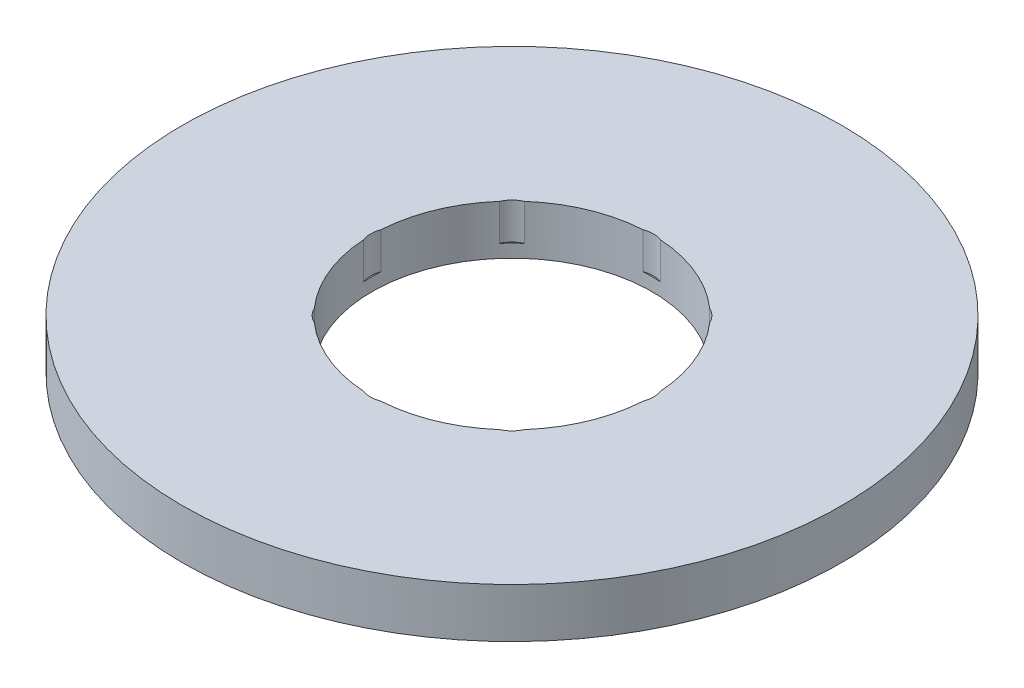
SolidWorks part; units mm, degrees
ref_plane "Front Plane" through (0, 0, 0) normal (0, 0, 1) x (1, 0, 0)
ref_plane "Top Plane" through (0, 0, 0) normal (0, 1, 0) x (1, 0, 0)
ref_plane "Right Plane" through (0, 0, 0) normal (1, 0, 0) x (0, 0, -1)
sketch "Sketch1" plane through (0, 0, 0) normal (0, 1, 0) x (1, 0, 0)
  circle A0 centre (0, 0) radius 100
  dimension "FLANGE_OD" = 200
extrude "Boss-Extrude1" add sketch "Sketch1" along normal blind 15
sketch "Sketch2" plane through (0, 0, 0) normal (0, 1, 0) x (1, 0, 0)
  circle A0 centre (0, 0) radius 42.5
  dimension "BORE_D" = 85
extrude "Cut-Extrude1" cut sketch "Sketch2" along normal through all
sketch "Sketch3" plane through (0, 15, 0) normal (0, 1, 0) x (1, 0, 0)
  circle A0 centre (0, 0) radius 35.195 construction
  circle A1 centre (-35.195, 0) radius 7.7009
  dimension "BOLT_D" = 15.4018
  dimension "BOLT_PCD" = 70.39
extrude "Cut-Extrude2" cut sketch "Sketch3" against normal blind 11.0441
pattern_circular "CirPattern1" count 8 over 360 about axis through (0, 0, 0) along (0, 1, 0) of "Cut-Extrude2"
